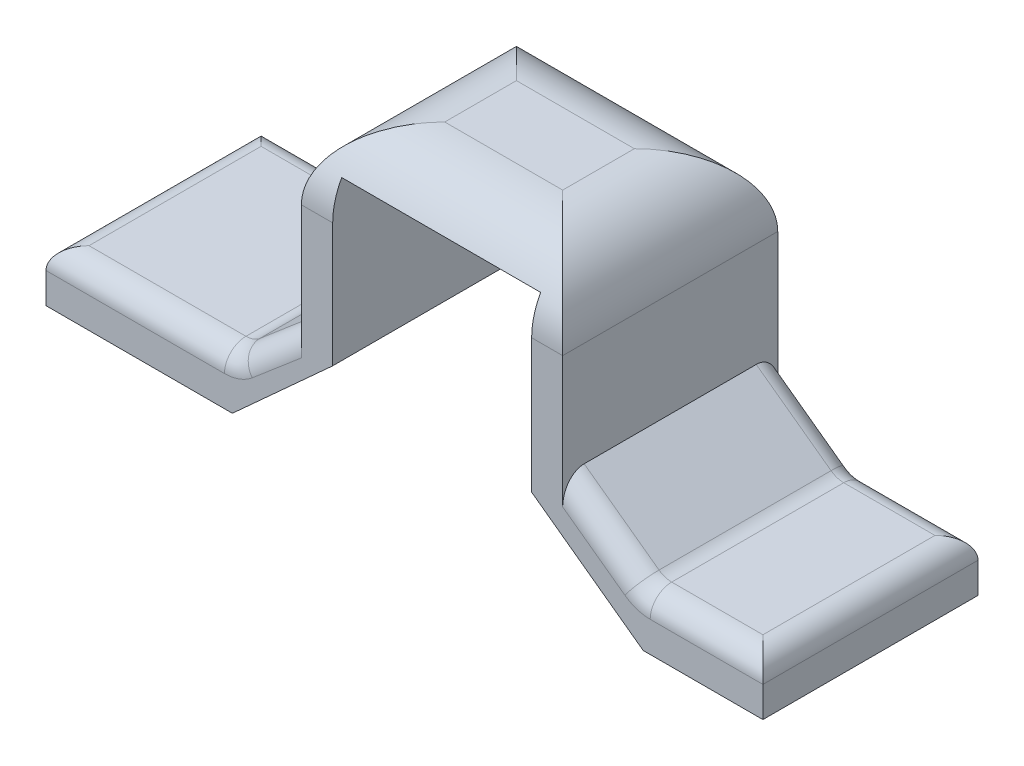
SolidWorks part; units mm, degrees
material "1060 合金"
ref_plane "前视基准面" through (0, 0, 0) normal (0, 0, 1) x (1, 0, 0)
ref_plane "上视基准面" through (0, 0, 0) normal (0, 1, 0) x (1, 0, 0)
ref_plane "右视基准面" through (0, 0, 0) normal (1, 0, 0) x (0, 0, -1)
sketch "草图1" plane through (0, 0, 0) normal (0, 0, 1) x (1, 0, 0)
  line L0 (0, 0) -> (1, 0)
  line L1 (1, 0) -> (1, 0.4)
  line L2 (1, 0.4) -> (0, 0.4)
  line L3 (0, 0.4) -> (0, 0)
  dimension "D1" = 1
extrude "凸台-拉伸1" add sketch "草图1" along normal blind 0.3
sketch "草图2" plane through (0, 0, 0.3) normal (0, 0, 1) x (1, 0, 0)
  line L0 (0, 0.0725) -> (0.2599, 0.0725)
  line L1 (0, 0.4) -> (0, 0) construction
  line L2 (0.2599, 0.0725) -> (0.3562, 0.1544)
  line L3 (0.3562, 0.1544) -> (0.3562, 0.4)
  line L4 (1, 0.4) -> (0, 0.4) construction
  line L5 (0.3562, 0.4) -> (0.7207, 0.4)
  line L6 (0.7207, 0.4) -> (0.7207, 0.1544)
  line L7 (0.7207, 0.1544) -> (0.833, 0.0725)
  line L8 (0.833, 0.0725) -> (1, 0.0725)
  line L9 (1, 0) -> (1, 0.4) construction
  line L10 (1, 0.0725) -> (1, 0)
  line L11 (1, 0) -> (0.833, 0)
  line L12 (0, 0) -> (1, 0) construction
  line L13 (0.833, 0) -> (0.6774, 0.1134)
  line L14 (0.6774, 0.1134) -> (0.6774, 0.3485)
  line L15 (0.6774, 0.3485) -> (0.3999, 0.3485)
  line L16 (0.3999, 0.3485) -> (0.3999, 0.1273)
  line L17 (0.3999, 0.1273) -> (0.2599, 0)
  line L18 (0.2599, 0) -> (0, 0)
  line L19 (0, 0) -> (0, 0.0725)
extrude "切除-拉伸1" cut sketch "草图2" against normal blind 0.7 flip side to cut
fillet "圆角1" radius 0.1 4 edges at (0.5384, 0.4, 0) (0.7207, 0.4, 0.15) (0.5384, 0.4, 0.3) (0.3562, 0.4, 0.15)
fillet "圆角2" radius 0.03 12 edges at (0.7768, 0.1134, 0) (0.7768, 0.1134, 0.3) (0.3081, 0.1134, 0) (0.3081, 0.1134, 0.3) (0.833, 0.0725, 0.15) (0.9165, 0.0725, 0) (1, 0.0725, 0.15) (0.9165, 0.0725, 0.3) (0, 0.0725, 0.15) (0.13, 0.0725, 0) (0.2599, 0.0725, 0.15) (0.13, 0.0725, 0.3)
